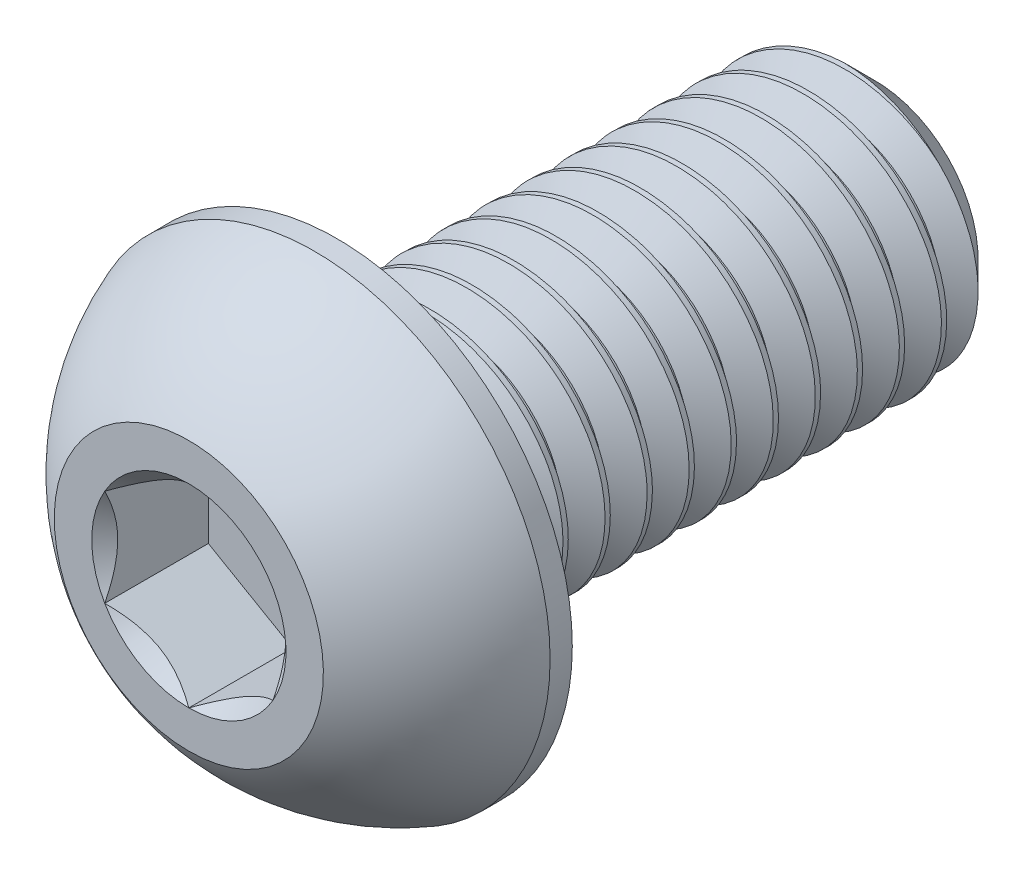
SolidWorks part; units mm, degrees
note: '?' marks a value the reader was unsure of.
ref_plane "Front" through (0, 0, 0) normal (0, 0, 1) x (1, 0, 0)
ref_plane "Top" through (0, 0, 0) normal (0, 1, 0) x (1, 0, 0)
ref_plane "Right" through (0, 0, 0) normal (1, 0, 0) x (0, 0, -1)
sketch "Sketch1" plane through (0, 0, 0) normal (1, 0, 0) x (0, 0, -1)
  line L2 (4.4, 4) -> (20.4, 4)
  line L3 (20.4, 4) -> (20.4, 0)
  line L4 (20.4, 0) -> (4.4, 0)
  line L6 (3.74, 7) -> (4.4, 7) construction
  line L7 (20.4, 4) -> (20.4, -4) construction
  line L8 (0, 0) -> (4.4, 0) construction
  line L9 (4.4, 7) -> (4.4, -7) construction
  line L11 (4.4, 4) -> (4.4, 0)
  line L13 (0, 2.5) -> (0, -2.5) construction
  line L14 (0, 2.5) -> (0, 4) construction
  arc A3 (0, 4) -> (3.74, 7) centre (6.2818, 0) cw construction
  dimension "D1" = 0.66
revolve "Revolve1" add sketch "Sketch1" angle 360 mid plane about L4
sketch "Sketch3" plane through (0, 0, -20.4) normal (0, 0, -1) x (-1, 0, 0)
  circle A0 centre (0, 0) radius 4
curve "Helix/Spiral1" pitch 1.25 height 17.25 turns 13.8
chamfer "Chamfer1" distance 0.9375 angle 45 1 edges at (-4, 0, -20.4)
sketch "Sketch7" plane through (0, 0, 0) normal (1, 0, 0) x (0, 0, -1)
  line L6 (3.74, 7) -> (4.4, 7) construction
  line L8 (0, 0) -> (4.4, 0) construction
  line L11 (4.4, 7) -> (4.4, -7) construction
  line L12 (3.74, 7) -> (4.4, 7)
  line L13 (0, 0) -> (4.4, 0)
  line L14 (0, 2.5) -> (0, -2.5) construction
  line L15 (4.4, 7) -> (4.4, 0)
  line L16 (0, 4) -> (0, 0)
  arc A2 (3.74, 7) -> (0, 4) centre (6.2818, 0) ccw construction
  arc A3 (3.74, 7) -> (0, 4) centre (6.2818, 0) ccw
revolve "Revolve2" add sketch "Sketch7" angle 360 mid plane about L13
sketch "Sketch5" plane through (0, 0, 0) normal (0, 0, 1) x (1, 0, 0)
  line L1 (2.5, -1.4434) -> (2.5, 1.4434)
  line L2 (2.5, 1.4434) -> (0, 2.8868)
  line L3 (0, 2.8868) -> (-2.5, 1.4434)
  line L4 (-2.5, 1.4434) -> (-2.5, -1.4434)
  line L5 (-2.5, -1.4434) -> (0, -2.8868)
  line L6 (0, -2.8868) -> (2.5, -1.4434)
  circle A0 centre (0, 0) radius 2.5 construction
extrude "Cut-Extrude2" cut sketch "Sketch5" against normal blind 3.08
sketch "Sketch6" plane through (0, 0, 0) normal (0, 0, 1) x (1, 0, 0)
  circle A0 centre (0, 0) radius 2.8868
extrude "Cut-Extrude3" cut sketch "Sketch6" against normal blind 3.08 draft 45
sketch "Sketch2" plane through (0, 0, 0) normal (1, 0, 0) x (0, 0, -1)
  line L0 (19.4625, 4) -> (20.5562, 4)
  line L1 (20.5562, 4) -> (20.0875, 3.1881)
  line L2 (20.0875, 3.1881) -> (19.9312, 3.1881)
  line L3 (19.9312, 3.1881) -> (19.4625, 4)
  line L4 (19.6969, 3.5941) -> (20.3219, 3.5941) construction
  dimension "D1" = 60
  dimension "D2" = 0.1562
  dimension "D3" = 0.625
sweep "Cut-Sweep1" cut profiles "Sketch2" path "Helix/Spiral1"
sketch "Sketch10" plane through (0, 0, 0) normal (1, 0, 0) x (0, 0, -1)
  line L0 (20.4, 4) -> (20.4, -4) construction
  point P0 (18.525, -4)
  dimension "D1" = 1.875
ref_axis "Center Axis 1" through (0, 0, -8.1113) along (0, 0, 1)?
ref_plane "Contact Plane 1" through (0, 0, -4.4) normal (0, 0, -1) x (-1, 0, 0)
ref_plane "Contact Plane 2" through (0, 0, 0) normal (0, 0, 1) x (1, 0, 0)
equation "\"D3@Helix/Spiral1\" = \"Lg@Sketch1\" + \"D4@Helix/Spiral1\""
equation "\"D2@Sketch2\" = \"D4@Helix/Spiral1\" * .125"
equation "\"D3@Sketch2\" = \"D4@Helix/Spiral1\" * .5"
equation "\"D1@Chamfer1\" = \"D4@Helix/Spiral1\" * .75"
equation "\"D1@Cut-Extrude2\" = \"Head Ht@Sketch1\" * .7"
equation "\"D1@Sketch1\" = \"Head Ht@Sketch1\" * .15"
equation "\"D1@Sketch10\" = \"D4@Helix/Spiral1\" * 1.5"
equation "\"D1@Cut-Extrude3\" = \"D1@Cut-Extrude2\""
